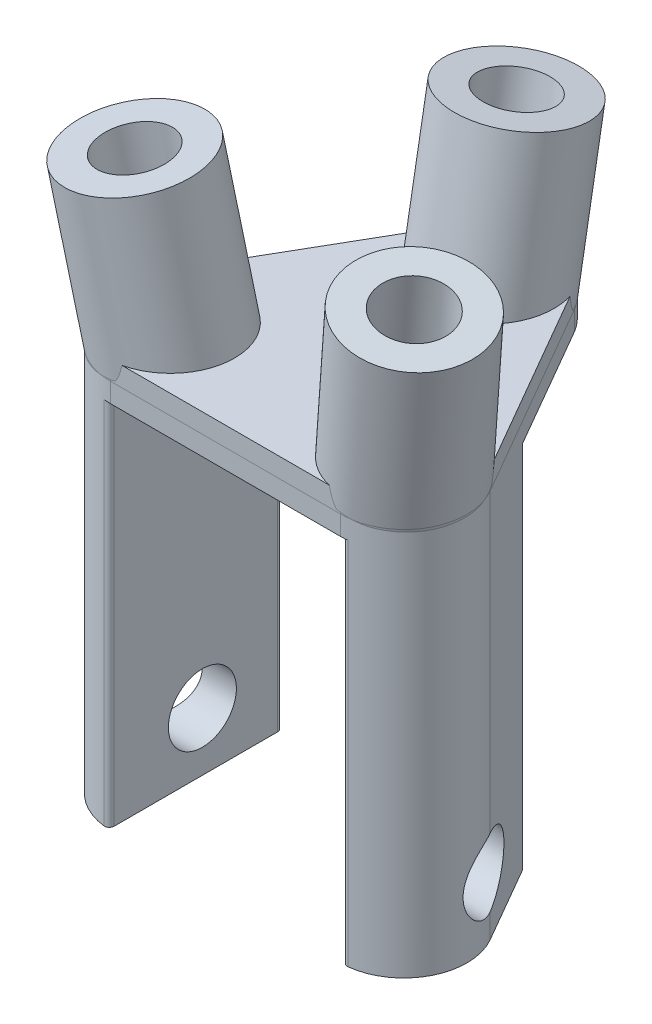
SolidWorks part; units mm, degrees
ref_plane "Front Plane" through (0, 0, 0) normal (0, 0, 1) x (1, 0, 0)
ref_plane "Top Plane" through (0, 0, 0) normal (0, 1, 0) x (1, 0, 0)
ref_plane "Right Plane" through (0, 0, 0) normal (1, 0, 0) x (0, 0, -1)
sketch "Sketch1" plane through (0, 0, 0) normal (0, 1, 0) x (1, 0, 0)
  line L0 (5.7735, 3.3333) -> (-11.547, -6.6667) construction
  line L1 (0, 13.3333) -> (-11.547, -6.6667)
  line L2 (-11.547, -6.6667) -> (11.547, -6.6667)
  line L3 (11.547, -6.6667) -> (0, 13.3333)
  line L4 (0, 13.3333) -> (0, -6.6667) construction
  line L5 (-5.7735, 3.3333) -> (11.547, -6.6667) construction
  circle A0 centre (0, 0) radius 6.6667 construction
  dimension "D1" = 20
extrude "Boss-Extrude1" add sketch "Sketch1" along normal blind 1
ref_axis "Axis1" through (-5.7735, 1, -3.3333) along (1, 0, 0)
ref_axis "Axis2" through (0, 0, 0) along (0, 1, 0)
ref_plane "Plane1" through (0, 1.5399, -0.2715) normal (0, 0.9848, -0.1736) x (1, 0, 0)
ref_plane "Plane2" through (0, 3.25, -0.5731) normal (0, 0.9848, -0.1736) x (1, 0, 0)
sketch "Sketch2" plane through (0, 1.5399, -0.2715) normal (0, 0.9848, -0.1736) x (1, 0, 0)
  line L0 (0, 13.1308) -> (0, -6.5654) construction
  line L1 (0, 13.1308) -> (-11.547, -6.5654) construction
  circle A0 centre (0, 6.7047) radius 3.25
  circle A1 centre (0, 6.7047) radius 1.75
  dimension "D1" = 1.5
  dimension "D2" = 3.5
extrude "Boss-Extrude2" add sketch "Sketch2" along normal blind 6.5 and the other way blind 1.75 from surface starting at plane "Plane2"
pattern_circular "CirPattern4" count 3 over 360 about axis through (0, 0, 0) along (0, 1, 0) of "Boss-Extrude2"
sketch "Sketch3" plane through (0, 0, 0) normal (0, 1, 0) x (1, 0, 0)
  line L0 (0, 13.3333) -> (-11.547, -6.6667)
  line L1 (-11.547, -6.6667) -> (11.547, -6.6667)
  line L2 (11.547, -6.6667) -> (0, 13.3333)
extrude "Boss-Extrude3" add sketch "Sketch3" against normal blind 20
sketch "Sketch5" plane through (0, 0, 0) normal (0, 0, 1) x (1, 0, 0)
  line L0 (-11.547, 0) -> (11.547, 0) construction
  line L1 (-6, -1) -> (6, -1)
  line L2 (-6, -1) -> (-6, -20)
  line L3 (-6, -20) -> (6, -20)
  line L4 (6, -1) -> (6, -20)
  line L5 (-11.547, -20) -> (11.547, -20) construction
  point P6 (0, -1)
  dimension "D1" = 1
  dimension "D2" = 0
  dimension "D3" = 12
extrude "Cut-Extrude1" cut sketch "Sketch5" along normal through all and the other way through all
sketch "Sketch6" plane through (0, 0, 0) normal (1, 0, 0) x (0, 0, -1)
  line L0 (-6.6667, -17) -> (2.941, -17) construction
  line L1 (-6.6667, 1) -> (-6.6667, -20) construction
  line L2 (2.941, -1) -> (2.941, -20) construction
  line L3 (13.3333, -1) -> (2.941, -1) construction
  circle A0 centre (-1.8628, -17) radius 1.75
  dimension "D2" = 3.5
  dimension "D1" = 16
extrude "Cut-Extrude2" cut sketch "Sketch6" against normal through all both and the other way through all
fillet "Fillet1" radius 3.25 3 edges at (-11.547, -9.5, 6.6667) (11.547, -9.5, 6.6667) (0, 0, -13.3333)
fillet "Fillet2" radius 0.25 4 edges at (6, -10.5, 6.6656) (-6, -10.5, 6.6656) (-6, -10.5, -2.941) (6, -10.5, -2.941)
split "Split1" trim tools "Top Plane" bodies to split 109 resulting bodies 110 111
